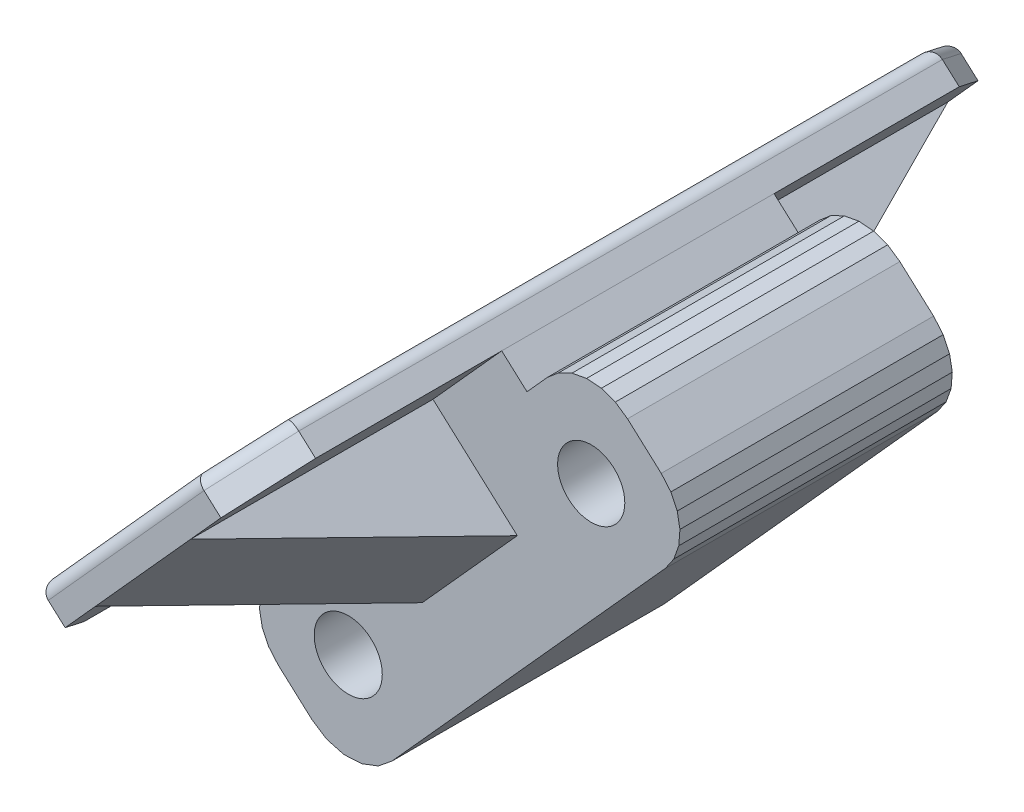
SolidWorks part; units mm, degrees
ref_plane "Front Plane" through (0, 0, 0) normal (0, 0, 1) x (1, 0, 0)
ref_plane "Top Plane" through (0, 0, 0) normal (0, 1, 0) x (1, 0, 0)
ref_plane "Right Plane" through (0, 0, 0) normal (1, 0, 0) x (0, 0, -1)
sketch "Model" plane through (0, 0, 0) normal (0, 0, 1) x (1, 0, 0)
  line L0 (51.8376, 63.8225) -> (52.4846, 63.9077) construction
  line L1 (52.4846, 63.9077) -> (53.0876, 64.1574) construction
  line L2 (53.0876, 64.1574) -> (53.6053, 64.5547) construction
  line L3 (53.6053, 64.5547) -> (54.0026, 65.0725) construction
  line L4 (54.0026, 65.0725) -> (54.2524, 65.6755) construction
  line L5 (54.2524, 65.6755) -> (54.3376, 66.3225) construction
  line L6 (54.3376, 66.3225) -> (54.3376, 68.3225) construction
  line L7 (54.3376, 68.3225) -> (54.2524, 68.9696) construction
  line L8 (54.2524, 68.9696) -> (54.0026, 69.5725) construction
  line L9 (54.0026, 69.5725) -> (53.6053, 70.0903) construction
  line L10 (53.6053, 70.0903) -> (53.0876, 70.4876) construction
  line L11 (53.0876, 70.4876) -> (52.4846, 70.7373) construction
  line L12 (52.4846, 70.7373) -> (51.8376, 70.8225) construction
  line L13 (51.8376, 70.8225) -> (33.8376, 70.8225) construction
  line L14 (33.8376, 70.8225) -> (33.1905, 70.7373) construction
  line L15 (33.1905, 70.7373) -> (32.5876, 70.4876) construction
  line L16 (32.5876, 70.4876) -> (32.0698, 70.0903) construction
  line L17 (32.0698, 70.0903) -> (31.6725, 69.5725) construction
  line L18 (31.6725, 69.5725) -> (31.4227, 68.9696) construction
  line L19 (31.4227, 68.9696) -> (31.3376, 68.3225) construction
  line L20 (31.3376, 68.3225) -> (31.3376, 66.3225) construction
  line L21 (31.3376, 66.3225) -> (31.4227, 65.6755) construction
  line L22 (31.4227, 65.6755) -> (31.6725, 65.0725) construction
  line L23 (31.6725, 65.0725) -> (32.0698, 64.5547) construction
  line L24 (32.0698, 64.5547) -> (32.5876, 64.1574) construction
  line L25 (32.5876, 64.1574) -> (33.1905, 63.9077) construction
  line L26 (33.1905, 63.9077) -> (33.8376, 63.8225) construction
  line L27 (33.8376, 63.8225) -> (51.8376, 63.8225) construction
  line L28 (83.8376, 63.8225) -> (84.4846, 63.9077) construction
  line L29 (84.4846, 63.9077) -> (85.0876, 64.1574) construction
  line L30 (85.0876, 64.1574) -> (85.6053, 64.5547) construction
  line L31 (85.6053, 64.5547) -> (86.0026, 65.0725) construction
  line L32 (86.0026, 65.0725) -> (86.2524, 65.6755) construction
  line L33 (86.2524, 65.6755) -> (86.3376, 66.3225) construction
  line L34 (86.3376, 66.3225) -> (86.3376, 68.3225) construction
  line L35 (86.3376, 68.3225) -> (86.2524, 68.9696) construction
  line L36 (86.2524, 68.9696) -> (86.0026, 69.5725) construction
  line L37 (86.0026, 69.5725) -> (85.6053, 70.0903) construction
  line L38 (85.6053, 70.0903) -> (85.0876, 70.4876) construction
  line L39 (85.0876, 70.4876) -> (84.4846, 70.7373) construction
  line L40 (84.4846, 70.7373) -> (83.8376, 70.8225) construction
  line L41 (83.8376, 70.8225) -> (65.8376, 70.8225) construction
  line L42 (65.8376, 70.8225) -> (65.1905, 70.7373) construction
  line L43 (65.1905, 70.7373) -> (64.5876, 70.4876) construction
  line L44 (64.5876, 70.4876) -> (64.0698, 70.0903) construction
  line L45 (64.0698, 70.0903) -> (63.6725, 69.5725) construction
  line L46 (63.6725, 69.5725) -> (63.4227, 68.9696) construction
  line L47 (63.4227, 68.9696) -> (63.3376, 68.3225) construction
  line L48 (63.3376, 68.3225) -> (63.3376, 66.3225) construction
  line L49 (63.3376, 66.3225) -> (63.4227, 65.6755) construction
  line L50 (63.4227, 65.6755) -> (63.6725, 65.0725) construction
  line L51 (63.6725, 65.0725) -> (64.0698, 64.5547) construction
  line L52 (64.0698, 64.5547) -> (64.5876, 64.1574) construction
  line L53 (64.5876, 64.1574) -> (65.1905, 63.9077) construction
  line L54 (65.1905, 63.9077) -> (65.8376, 63.8225) construction
  line L55 (65.8376, 63.8225) -> (83.8376, 63.8225) construction
  line L56 (115.8376, 63.8225) -> (116.4846, 63.9077) construction
  line L57 (116.4846, 63.9077) -> (117.0876, 64.1574) construction
  line L58 (117.0876, 64.1574) -> (117.6053, 64.5547) construction
  line L59 (117.6053, 64.5547) -> (118.0026, 65.0725) construction
  line L60 (118.0026, 65.0725) -> (118.2524, 65.6755) construction
  line L61 (118.2524, 65.6755) -> (118.3376, 66.3225) construction
  line L62 (118.3376, 66.3225) -> (118.3376, 68.3225) construction
  line L63 (118.3376, 68.3225) -> (118.2524, 68.9696) construction
  line L64 (118.2524, 68.9696) -> (118.0026, 69.5725) construction
  line L65 (118.0026, 69.5725) -> (117.6053, 70.0903) construction
  line L66 (117.6053, 70.0903) -> (117.0876, 70.4876) construction
  line L67 (117.0876, 70.4876) -> (116.4846, 70.7373) construction
  line L68 (116.4846, 70.7373) -> (115.8376, 70.8225) construction
  line L69 (115.8376, 70.8225) -> (97.8376, 70.8225) construction
  line L70 (97.8376, 70.8225) -> (97.1905, 70.7373) construction
  line L71 (97.1905, 70.7373) -> (96.5876, 70.4876) construction
  line L72 (96.5876, 70.4876) -> (96.0698, 70.0903) construction
  line L73 (96.0698, 70.0903) -> (95.6725, 69.5725) construction
  line L74 (95.6725, 69.5725) -> (95.4227, 68.9696) construction
  line L75 (95.4227, 68.9696) -> (95.3376, 68.3225) construction
  line L76 (95.3376, 68.3225) -> (95.3376, 66.3225) construction
  line L77 (95.3376, 66.3225) -> (95.4227, 65.6755) construction
  line L78 (95.4227, 65.6755) -> (95.6725, 65.0725) construction
  line L79 (95.6725, 65.0725) -> (96.0698, 64.5547) construction
  line L80 (96.0698, 64.5547) -> (96.5876, 64.1574) construction
  line L81 (96.5876, 64.1574) -> (97.1905, 63.9077) construction
  line L82 (97.1905, 63.9077) -> (97.8376, 63.8225) construction
  line L83 (97.8376, 63.8225) -> (115.8376, 63.8225) construction
  line L84 (147.8376, 63.8225) -> (148.4846, 63.9077) construction
  line L85 (148.4846, 63.9077) -> (149.0876, 64.1574) construction
  line L86 (149.0876, 64.1574) -> (149.6053, 64.5547) construction
  line L87 (149.6053, 64.5547) -> (150.0026, 65.0725) construction
  line L88 (150.0026, 65.0725) -> (150.2524, 65.6755) construction
  line L89 (150.2524, 65.6755) -> (150.3376, 66.3225) construction
  line L90 (150.3376, 66.3225) -> (150.3376, 68.3225) construction
  line L91 (150.3376, 68.3225) -> (150.2524, 68.9696) construction
  line L92 (150.2524, 68.9696) -> (150.0026, 69.5725) construction
  line L93 (150.0026, 69.5725) -> (149.6053, 70.0903) construction
  line L94 (149.6053, 70.0903) -> (149.0876, 70.4876) construction
  line L95 (149.0876, 70.4876) -> (148.4846, 70.7373) construction
  line L96 (148.4846, 70.7373) -> (147.8376, 70.8225) construction
  line L97 (147.8376, 70.8225) -> (129.8376, 70.8225) construction
  line L98 (129.8376, 70.8225) -> (129.1905, 70.7373) construction
  line L99 (129.1905, 70.7373) -> (128.5876, 70.4876) construction
  line L100 (128.5876, 70.4876) -> (128.0698, 70.0903) construction
  line L101 (128.0698, 70.0903) -> (127.6725, 69.5725) construction
  line L102 (127.6725, 69.5725) -> (127.4227, 68.9696) construction
  line L103 (127.4227, 68.9696) -> (127.3376, 68.3225) construction
  line L104 (127.3376, 68.3225) -> (127.3376, 66.3225) construction
  line L105 (127.3376, 66.3225) -> (127.4227, 65.6755) construction
  line L106 (127.4227, 65.6755) -> (127.6725, 65.0725) construction
  line L107 (127.6725, 65.0725) -> (128.0698, 64.5547) construction
  line L108 (128.0698, 64.5547) -> (128.5876, 64.1574) construction
  line L109 (128.5876, 64.1574) -> (129.1905, 63.9077) construction
  line L110 (129.1905, 63.9077) -> (129.8376, 63.8225) construction
  line L111 (129.8376, 63.8225) -> (147.8376, 63.8225) construction
  line L112 (71.0729, 2.088) -> (71.72, 2.1732) construction
  line L113 (71.72, 2.1732) -> (72.3229, 2.4229) construction
  line L114 (72.3229, 2.4229) -> (72.8407, 2.8202) construction
  line L115 (72.8407, 2.8202) -> (73.238, 3.338) construction
  line L116 (73.238, 3.338) -> (73.4877, 3.9409) construction
  line L117 (73.4877, 3.9409) -> (73.5729, 4.588) construction
  line L118 (73.5729, 4.588) -> (73.5729, 6.588) construction
  line L119 (73.5729, 6.588) -> (73.4877, 7.235) construction
  line L120 (73.4877, 7.235) -> (73.238, 7.838) construction
  line L121 (73.238, 7.838) -> (72.8407, 8.3557) construction
  line L122 (72.8407, 8.3557) -> (72.3229, 8.753) construction
  line L123 (72.3229, 8.753) -> (71.72, 9.0028) construction
  line L124 (71.72, 9.0028) -> (71.0729, 9.088) construction
  line L125 (71.0729, 9.088) -> (53.0729, 9.088) construction
  line L126 (53.0729, 9.088) -> (52.4259, 9.0028) construction
  line L127 (52.4259, 9.0028) -> (51.8229, 8.753) construction
  line L128 (51.8229, 8.753) -> (51.3052, 8.3557) construction
  line L129 (51.3052, 8.3557) -> (50.9079, 7.838) construction
  line L130 (50.9079, 7.838) -> (50.6581, 7.235) construction
  line L131 (50.6581, 7.235) -> (50.5729, 6.588) construction
  line L132 (50.5729, 6.588) -> (50.5729, 4.588) construction
  line L133 (50.5729, 4.588) -> (50.6581, 3.9409) construction
  line L134 (50.6581, 3.9409) -> (50.9079, 3.338) construction
  line L135 (50.9079, 3.338) -> (51.3052, 2.8202) construction
  line L136 (51.3052, 2.8202) -> (51.8229, 2.4229) construction
  line L137 (51.8229, 2.4229) -> (52.4259, 2.1732) construction
  line L138 (52.4259, 2.1732) -> (53.0729, 2.088) construction
  line L139 (53.0729, 2.088) -> (71.0729, 2.088) construction
  line L140 (103.0729, 2.088) -> (103.72, 2.1732) construction
  line L141 (103.72, 2.1732) -> (104.3229, 2.4229) construction
  line L142 (104.3229, 2.4229) -> (104.8407, 2.8202) construction
  line L143 (104.8407, 2.8202) -> (105.238, 3.338) construction
  line L144 (105.238, 3.338) -> (105.4877, 3.9409) construction
  line L145 (105.4877, 3.9409) -> (105.5729, 4.588) construction
  line L146 (105.5729, 4.588) -> (105.5729, 6.588) construction
  line L147 (105.5729, 6.588) -> (105.4877, 7.235) construction
  line L148 (105.4877, 7.235) -> (105.238, 7.838) construction
  line L149 (105.238, 7.838) -> (104.8407, 8.3557) construction
  line L150 (104.8407, 8.3557) -> (104.3229, 8.753) construction
  line L151 (104.3229, 8.753) -> (103.72, 9.0028) construction
  line L152 (103.72, 9.0028) -> (103.0729, 9.088) construction
  line L153 (103.0729, 9.088) -> (85.0729, 9.088) construction
  line L154 (85.0729, 9.088) -> (84.4259, 9.0028) construction
  line L155 (84.4259, 9.0028) -> (83.8229, 8.753) construction
  line L156 (83.8229, 8.753) -> (83.3052, 8.3557) construction
  line L157 (83.3052, 8.3557) -> (82.9079, 7.838) construction
  line L158 (82.9079, 7.838) -> (82.6581, 7.235) construction
  line L159 (82.6581, 7.235) -> (82.5729, 6.588) construction
  line L160 (82.5729, 6.588) -> (82.5729, 4.588) construction
  line L161 (82.5729, 4.588) -> (82.6581, 3.9409) construction
  line L162 (82.6581, 3.9409) -> (82.9079, 3.338) construction
  line L163 (82.9079, 3.338) -> (83.3052, 2.8202) construction
  line L164 (83.3052, 2.8202) -> (83.8229, 2.4229) construction
  line L165 (83.8229, 2.4229) -> (84.4259, 2.1732) construction
  line L166 (84.4259, 2.1732) -> (85.0729, 2.088) construction
  line L167 (85.0729, 2.088) -> (103.0729, 2.088) construction
  line L168 (135.0729, 2.088) -> (135.72, 2.1732) construction
  line L169 (135.72, 2.1732) -> (136.3229, 2.4229) construction
  line L170 (136.3229, 2.4229) -> (136.8407, 2.8202) construction
  line L171 (136.8407, 2.8202) -> (137.238, 3.338) construction
  line L172 (137.238, 3.338) -> (137.4877, 3.9409) construction
  line L173 (137.4877, 3.9409) -> (137.5729, 4.588) construction
  line L174 (137.5729, 4.588) -> (137.5729, 6.588) construction
  line L175 (137.5729, 6.588) -> (137.4877, 7.235) construction
  line L176 (137.4877, 7.235) -> (137.238, 7.838) construction
  line L177 (137.238, 7.838) -> (136.8407, 8.3557) construction
  line L178 (136.8407, 8.3557) -> (136.3229, 8.753) construction
  line L179 (136.3229, 8.753) -> (135.72, 9.0028) construction
  line L180 (135.72, 9.0028) -> (135.0729, 9.088) construction
  line L181 (135.0729, 9.088) -> (117.0729, 9.088) construction
  line L182 (117.0729, 9.088) -> (116.4259, 9.0028) construction
  line L183 (116.4259, 9.0028) -> (115.8229, 8.753) construction
  line L184 (115.8229, 8.753) -> (115.3052, 8.3557) construction
  line L185 (115.3052, 8.3557) -> (114.9079, 7.838) construction
  line L186 (114.9079, 7.838) -> (114.6581, 7.235) construction
  line L187 (114.6581, 7.235) -> (114.5729, 6.588) construction
  line L188 (114.5729, 6.588) -> (114.5729, 4.588) construction
  line L189 (114.5729, 4.588) -> (114.6581, 3.9409) construction
  line L190 (114.6581, 3.9409) -> (114.9079, 3.338) construction
  line L191 (114.9079, 3.338) -> (115.3052, 2.8202) construction
  line L192 (115.3052, 2.8202) -> (115.8229, 2.4229) construction
  line L193 (115.8229, 2.4229) -> (116.4259, 2.1732) construction
  line L194 (116.4259, 2.1732) -> (117.0729, 2.088) construction
  line L195 (117.0729, 2.088) -> (135.0729, 2.088) construction
  line L196 (167.0729, 2.088) -> (167.72, 2.1732) construction
  line L197 (167.72, 2.1732) -> (168.3229, 2.4229) construction
  line L198 (168.3229, 2.4229) -> (168.8407, 2.8202) construction
  line L199 (168.8407, 2.8202) -> (169.238, 3.338) construction
  line L200 (169.238, 3.338) -> (169.4877, 3.9409) construction
  line L201 (169.4877, 3.9409) -> (169.5729, 4.588) construction
  line L202 (169.5729, 4.588) -> (169.5729, 6.588) construction
  line L203 (169.5729, 6.588) -> (169.4877, 7.235) construction
  line L204 (169.4877, 7.235) -> (169.238, 7.838) construction
  line L205 (169.238, 7.838) -> (168.8407, 8.3557) construction
  line L206 (168.8407, 8.3557) -> (168.3229, 8.753) construction
  line L207 (168.3229, 8.753) -> (167.72, 9.0028) construction
  line L208 (167.72, 9.0028) -> (167.0729, 9.088) construction
  line L209 (167.0729, 9.088) -> (149.0729, 9.088) construction
  line L210 (149.0729, 9.088) -> (148.4259, 9.0028) construction
  line L211 (148.4259, 9.0028) -> (147.8229, 8.753) construction
  line L212 (147.8229, 8.753) -> (147.3052, 8.3557) construction
  line L213 (147.3052, 8.3557) -> (146.9079, 7.838) construction
  line L214 (146.9079, 7.838) -> (146.6581, 7.235) construction
  line L215 (146.6581, 7.235) -> (146.5729, 6.588) construction
  line L216 (146.5729, 6.588) -> (146.5729, 4.588) construction
  line L217 (146.5729, 4.588) -> (146.6581, 3.9409) construction
  line L218 (146.6581, 3.9409) -> (146.9079, 3.338) construction
  line L219 (146.9079, 3.338) -> (147.3052, 2.8202) construction
  line L220 (147.3052, 2.8202) -> (147.8229, 2.4229) construction
  line L221 (147.8229, 2.4229) -> (148.4259, 2.1732) construction
  line L222 (148.4259, 2.1732) -> (149.0729, 2.088) construction
  line L223 (149.0729, 2.088) -> (167.0729, 2.088) construction
  line L224 (5.6444, 52.0867) -> (5.2748, 51.5489)
  line L225 (5.2748, 51.5489) -> (5.0569, 50.9337)
  line L226 (5.0569, 50.9337) -> (5.0057, 50.2831)
  line L227 (5.0057, 50.2831) -> (5.1246, 49.6414)
  line L228 (5.1246, 49.6414) -> (5.4056, 49.0523)
  line L229 (5.4056, 49.0523) -> (5.8295, 48.556)
  line L230 (5.8295, 48.556) -> (7.3157, 47.2178)
  line L231 (7.3157, 47.2178) -> (7.9717, 46.7918)
  line L232 (7.9717, 46.7918) -> (8.7273, 46.5893)
  line L233 (8.7273, 46.5893) -> (9.5084, 46.6303)
  line L234 (9.5084, 46.6303) -> (10.2386, 46.9106)
  line L235 (10.2386, 46.9106) -> (10.8464, 47.4028)
  line L236 (10.8464, 47.4028) -> (22.8908, 60.7794)
  line L237 (22.8908, 60.7794) -> (23.2604, 61.3173)
  line L238 (23.2604, 61.3173) -> (23.4783, 61.9325)
  line L239 (23.4783, 61.9325) -> (23.5295, 62.5831)
  line L240 (23.5295, 62.5831) -> (23.4106, 63.2248)
  line L241 (23.4106, 63.2248) -> (23.1296, 63.8138)
  line L242 (23.1296, 63.8138) -> (22.7058, 64.3101)
  line L243 (22.7058, 64.3101) -> (21.2195, 65.6484)
  line L244 (21.2195, 65.6484) -> (20.6816, 66.018)
  line L245 (20.6816, 66.018) -> (20.0664, 66.2359)
  line L246 (20.0664, 66.2359) -> (19.4158, 66.2871)
  line L247 (19.4158, 66.2871) -> (18.7741, 66.1681)
  line L248 (18.7741, 66.1681) -> (18.185, 65.8872)
  line L249 (18.185, 65.8872) -> (17.6888, 65.4633)
  line L250 (17.6888, 65.4633) -> (5.6444, 52.0867)
  line L251 (7.5126, 17.588) -> (7.7935, 16.999) construction
  line L252 (7.7935, 16.999) -> (8.2174, 16.5027) construction
  line L253 (8.2174, 16.5027) -> (8.7552, 16.1331) construction
  line L254 (8.7552, 16.1331) -> (9.3704, 15.9152) construction
  line L255 (9.3704, 15.9152) -> (10.021, 15.864) construction
  line L256 (10.021, 15.864) -> (10.6627, 15.9829) construction
  line L257 (10.6627, 15.9829) -> (12.5649, 16.601) construction
  line L258 (12.5649, 16.601) -> (13.1539, 16.8819) construction
  line L259 (13.1539, 16.8819) -> (13.6502, 17.3058) construction
  line L260 (13.6502, 17.3058) -> (14.0198, 17.8436) construction
  line L261 (14.0198, 17.8436) -> (14.2377, 18.4588) construction
  line L262 (14.2377, 18.4588) -> (14.2889, 19.1094) construction
  line L263 (14.2889, 19.1094) -> (14.17, 19.7512) construction
  line L264 (14.17, 19.7512) -> (8.6077, 36.8702) construction
  line L265 (8.6077, 36.8702) -> (8.3267, 37.4592) construction
  line L266 (8.3267, 37.4592) -> (7.9028, 37.9555) construction
  line L267 (7.9028, 37.9555) -> (7.365, 38.3251) construction
  line L268 (7.365, 38.3251) -> (6.7498, 38.543) construction
  line L269 (6.7498, 38.543) -> (6.0992, 38.5942) construction
  line L270 (6.0992, 38.5942) -> (5.4575, 38.4753) construction
  line L271 (5.4575, 38.4753) -> (3.5554, 37.8572) construction
  line L272 (3.5554, 37.8572) -> (2.9663, 37.5763) construction
  line L273 (2.9663, 37.5763) -> (2.47, 37.1524) construction
  line L274 (2.47, 37.1524) -> (2.1004, 36.6146) construction
  line L275 (2.1004, 36.6146) -> (1.8825, 35.9994) construction
  line L276 (1.8825, 35.9994) -> (1.8313, 35.3488) construction
  line L277 (1.8313, 35.3488) -> (1.9503, 34.7071) construction
  line L278 (1.9503, 34.7071) -> (7.5126, 17.588) construction
  line L279 (38.3234, 1.9565) -> (38.974, 1.9053) construction
  line L280 (38.974, 1.9053) -> (39.6157, 2.0243) construction
  line L281 (39.6157, 2.0243) -> (40.2048, 2.3052) construction
  line L282 (40.2048, 2.3052) -> (40.701, 2.7291) construction
  line L283 (40.701, 2.7291) -> (41.0707, 3.2669) construction
  line L284 (41.0707, 3.2669) -> (41.2885, 3.8821) construction
  line L285 (41.2885, 3.8821) -> (41.7044, 5.8384) construction
  line L286 (41.7044, 5.8384) -> (41.7556, 6.489) construction
  line L287 (41.7556, 6.489) -> (41.6366, 7.1308) construction
  line L288 (41.6366, 7.1308) -> (41.3557, 7.7198) construction
  line L289 (41.3557, 7.7198) -> (40.9318, 8.2161) construction
  line L290 (40.9318, 8.2161) -> (40.394, 8.5857) construction
  line L291 (40.394, 8.5857) -> (39.7788, 8.8036) construction
  line L292 (39.7788, 8.8036) -> (22.1721, 12.546) construction
  line L293 (22.1721, 12.546) -> (21.391, 12.5869) construction
  line L294 (21.391, 12.5869) -> (20.6355, 12.3845) construction
  line L295 (20.6355, 12.3845) -> (19.9795, 11.9585) construction
  line L296 (19.9795, 11.9585) -> (19.4873, 11.3506) construction
  line L297 (19.4873, 11.3506) -> (19.207, 10.6204) construction
  line L298 (19.207, 10.6204) -> (18.7911, 8.6641) construction
  line L299 (18.7911, 8.6641) -> (18.7399, 8.0135) construction
  line L300 (18.7399, 8.0135) -> (18.8589, 7.3718) construction
  line L301 (18.8589, 7.3718) -> (19.1398, 6.7827) construction
  line L302 (19.1398, 6.7827) -> (19.5637, 6.2865) construction
  line L303 (19.5637, 6.2865) -> (20.1015, 5.9168) construction
  line L304 (20.1015, 5.9168) -> (20.7167, 5.699) construction
  line L305 (20.7167, 5.699) -> (38.3234, 1.9565) construction
  circle A0 centre (34.8376, 67.3225) radius 1.5 construction
  circle A1 centre (50.8376, 67.3225) radius 1.5 construction
  circle A2 centre (66.8376, 67.3225) radius 1.5 construction
  circle A3 centre (82.8376, 67.3225) radius 1.5 construction
  circle A4 centre (98.8376, 67.3225) radius 1.5 construction
  circle A5 centre (114.8376, 67.3225) radius 1.5 construction
  circle A6 centre (130.8376, 67.3225) radius 1.5 construction
  circle A7 centre (146.8376, 67.3225) radius 1.5 construction
  circle A8 centre (54.0729, 5.588) radius 1.5 construction
  circle A9 centre (70.0729, 5.588) radius 1.5 construction
  circle A10 centre (86.0729, 5.588) radius 1.5 construction
  circle A11 centre (102.0729, 5.588) radius 1.5 construction
  circle A12 centre (118.0729, 5.588) radius 1.5 construction
  circle A13 centre (134.0729, 5.588) radius 1.5 construction
  circle A14 centre (150.0729, 5.588) radius 1.5 construction
  circle A15 centre (166.0729, 5.588) radius 1.5 construction
  circle A16 centre (19.6206, 62.3782) radius 1.48
  circle A17 centre (8.9146, 50.4879) radius 1.5
  circle A18 centre (5.588, 34.8376) radius 1.5 construction
  circle A19 centre (10.5322, 19.6206) radius 1.5 construction
  circle A20 centre (22.4226, 8.9146) radius 1.5 construction
  circle A21 centre (38.0729, 5.588) radius 1.5 construction
extrude "Boss-Extrude1" add sketch "Model" along normal blind 12
sketch "Sketch3" plane through (-22.7835, 20.5145, 0) normal (-0.7431, 0.6691, 0) x (0, 0, 1)
  line L0 (0, 51.4847) -> (12, 51.4847) construction
  line L3 (0, 60.4848) -> (0, 42.4847) construction
  line L5 (12, 60.4848) -> (12, 42.4847) construction
  line L6 (12, 51.4847) -> (6, 60.4848) construction
  line L7 (12, 60.4848) -> (0, 60.4848) construction
  line L9 (12, 59.1433) -> (0, 59.1433)
  line L10 (12, 59.1433) -> (12, 43.8262)
  line L11 (12, 43.8262) -> (0, 43.8262)
  line L12 (0, 59.1433) -> (0, 43.8262)
  line L13 (12, 59.1433) -> (0, 43.8262) construction
  line L14 (12, 43.8262) -> (0, 59.1433) construction
  point P6 (6, 51.4847)
extrude "Boss-Extrude2" add sketch "Sketch3" along normal blind 1.5
sketch "Sketch4" plane through (-23.8982, 21.5182, 0) normal (-0.7431, 0.6691, 0) x (0, 0, 1)
  line L0 (-10.68, 56.1126) -> (-10.68, 59.1126)
  line L3 (-10.68, 59.1126) -> (-7.68, 59.1126)
  line L5 (-10.68, 46.8568) -> (-10.68, 43.8568)
  line L6 (-10.68, 43.8568) -> (-7.68, 43.8568)
  line L7 (19.68, 59.1126) -> (-7.68, 59.1126)
  line L8 (22.68, 56.1126) -> (22.68, 46.8568)
  line L9 (19.68, 43.8568) -> (-7.68, 43.8568)
  line L10 (-10.68, 56.1126) -> (-10.68, 46.8568)
  line L11 (22.68, 59.1126) -> (-10.68, 43.8568) construction
  line L12 (22.68, 43.8568) -> (-10.68, 59.1126) construction
  line L13 (19.68, 43.8568) -> (22.68, 43.8568)
  line L14 (22.68, 43.8568) -> (22.68, 46.8568)
  line L15 (22.68, 56.1126) -> (22.68, 59.1126)
  line L16 (22.68, 59.1126) -> (19.68, 59.1126)
extrude "Boss-Extrude3" add sketch "Sketch4" along normal blind 1.5
sketch "Sketch9" plane through (29.346, 32.5919, 0) normal (-0.6691, -0.7431, 0) x (0.7431, -0.6691, 0)
  line L0 (-32.1583, 12) -> (-32.1583, 22.68)
  line L1 (-28.1582, 12) -> (-26.1583, 12) construction
  line L2 (-27.1583, 12) -> (-32.1583, 12)
  line L3 (-32.1583, 22.68) -> (-27.1583, 12)
extrude "Boss-Extrude4" add sketch "Sketch9" against normal blind 6.26 from offset 4.5 offset against normal yes
ref_point "Point1"
ref_point "Point2"
ref_axis "Axis1" through (21.9628, 64.9791, 6) along (-0.6691, -0.7431, 0)
ref_plane "Plane1" through (0, 0, 6) normal (0, 0, 1) x (1, 0, 0)
mirror "Mirror1" about plane through (0, 0, 6) normal (0, 0, 1) of "Boss-Extrude4"
chamfer "Chamfer1" distance 2.5 angle 45 4 edges at (4.8905, 54.6119, 22.68) (4.8905, 54.6119, -10.68) (15.0986, 65.9492, -10.68) (15.0986, 65.9492, 22.68)
fillet "Fillet2" radius 0.5 8 edges at (4.3331, 55.1138, 6) (13.7048, 65.5221, 21.43) (9.4372, 60.7824, 22.68) (5.1695, 56.0427, 21.43) (13.7048, 65.5221, -9.43) (5.1695, 56.0427, -9.43) (9.4372, 60.7824, -10.68) (14.5412, 66.451, 6)
sketch "Sketch10" plane through (-25.0129, 22.5219, 0) normal (-0.7431, 0.6691, 0) x (0, 0, 1)
  line L0 (-10.18, 51.4847) -> (22.18, 51.4847) construction
  line L1 (-10.18, 56.4055) -> (-10.18, 46.564) construction
  line L2 (22.18, 46.564) -> (22.18, 56.4055) construction
  line L3 (6, 58.6126) -> (6, 51.4847) construction
  line L4 (19.9729, 58.6126) -> (-7.9729, 58.6126) construction
  line L6 (19, 55.0487) -> (-7, 55.0487) construction
  line L7 (19, 53.0487) -> (-7, 53.0487)
  line L8 (19, 57.0487) -> (-7, 57.0487)
  line L9 (19, 47.9208) -> (-7, 47.9208) construction
  line L10 (19, 49.9208) -> (-7, 49.9208)
  line L11 (19, 45.9208) -> (-7, 45.9208)
  arc A0 (19, 53.0487) -> (19, 57.0487) centre (19, 55.0487) ccw
  arc A1 (-7, 57.0487) -> (-7, 53.0487) centre (-7, 55.0487) ccw
  arc A2 (19, 49.9208) -> (19, 45.9208) centre (19, 47.9208) cw
  arc A3 (-7, 45.9208) -> (-7, 49.9208) centre (-7, 47.9208) cw
  point P11 (6, 55.0487)
  point P19 (6, 47.9208)
extrude "Cut-Extrude1" cut sketch "Sketch10" against normal blind 1
